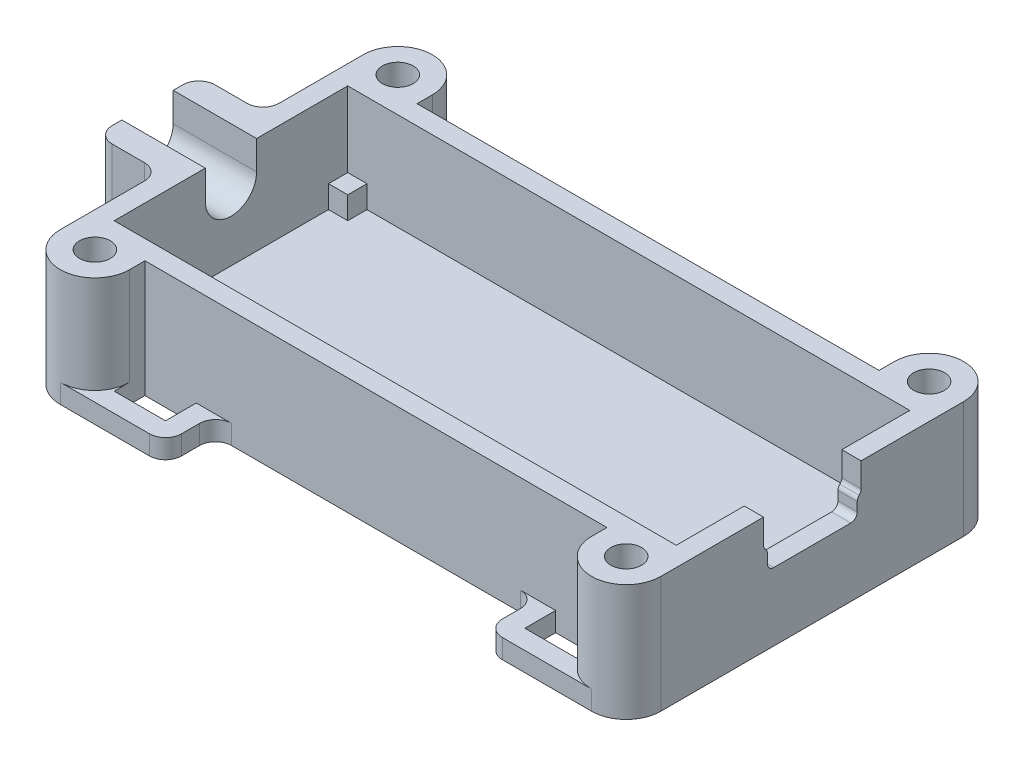
SolidWorks part; units mm, degrees
ref_plane "Front Plane" through (0, 0, 0) normal (0, 0, 1) x (1, 0, 0)
ref_plane "Top Plane" through (0, 0, 0) normal (0, 1, 0) x (1, 0, 0)
ref_plane "Right Plane" through (0, 0, 0) normal (1, 0, 0) x (0, 0, -1)
sketch "Sketch1" plane through (0, 0, 0) normal (0, 1, 0) x (1, 0, 0)
  line L0 (-21.9, 9.1) -> (-23.4, 9.1) construction
  line L1 (-21.9, 9.1) -> (21.9, 9.1)
  line L2 (-21.9, 9.1) -> (-21.9, -9.1)
  line L3 (-21.9, -9.1) -> (21.9, -9.1)
  line L4 (21.9, 9.1) -> (21.9, -9.1)
  line L5 (-21.9, 9.1) -> (21.9, -9.1) construction
  line L6 (-21.9, -9.1) -> (21.9, 9.1) construction
  line L7 (23.4, -10.6) -> (-23.4, -10.6)
  line L8 (23.4, -10.6) -> (23.4, 10.6)
  line L9 (23.4, 10.6) -> (-23.4, 10.6)
  line L10 (-23.4, -10.6) -> (-23.4, 10.6)
  line L11 (23.4, -10.6) -> (-23.4, 10.6) construction
  line L12 (23.4, 10.6) -> (-23.4, -10.6) construction
  line L13 (-21.9, 9.1) -> (-21.9, 10.6) construction
  line L14 (-19.5, 11.8) -> (-18, 11.8) construction
  line L15 (-23.4, 11.8) -> (-23.4, 10.6)
  line L16 (0, 30.5142) -> (0, -27.0472) construction
  line L17 (-40.1948, 0) -> (31.8876, 0) construction
  line L18 (-18, 11.8) -> (-18, 10.6)
  line L19 (18, 11.8) -> (18, 10.6)
  line L20 (23.4, 11.8) -> (23.4, 10.6)
  line L21 (23.4, -11.8) -> (23.4, -10.6)
  line L22 (18, -11.8) -> (18, -10.6)
  line L23 (-18, -11.8) -> (-18, -10.6)
  line L24 (-23.4, -11.8) -> (-23.4, -10.6)
  line L26 (-28.4, 4) -> (-23.4, 4)
  line L27 (-28.4, 4) -> (-28.4, -4)
  line L28 (-28.4, -4) -> (-23.4, -4)
  line L29 (-23.4, 4) -> (-23.4, -4)
  line L30 (-28.4, 4) -> (-23.4, -4) construction
  line L31 (-28.4, -4) -> (-23.4, 4) construction
  circle A0 centre (-20.7, 11.8) radius 1.2
  circle A1 centre (-20.7, 11.8) radius 2.7
  circle A2 centre (20.7, 11.8) radius 1.2
  circle A3 centre (20.7, 11.8) radius 2.7
  circle A4 centre (20.7, -11.8) radius 1.2
  circle A5 centre (20.7, -11.8) radius 2.7
  circle A6 centre (-20.7, -11.8) radius 1.2
  circle A7 centre (-20.7, -11.8) radius 2.7
  point P0 (0, 0)
  point P6 (0, 0)
  point P42 (-25.9, 0)
  dimension "D4" = 2.4
  dimension "D5" = 5
  dimension "D1" = 18.2
  dimension "D2" = 43.8
  dimension "D3" = 1.5
  dimension "D6" = 8
extrude "Boss-Extrude1" add sketch "Sketch1" along normal blind 7.6 contours A1 L9 L18 | L9 A1 A0 | A1 L15 L9 | L9 A3 L19 | A3 L9 A2 | L20 A3 L9 | A5 L7 L22 | A5 L7 A4 | A5 L21 L7 | L24 A7 L7 | A7 L7 A6 | L7 A7 L23 | L7 A7 L3 L2 L1 A1 L9 L10 | A7 L7 | L3 A7 L7 A5 | L7 A5 | A5 L7 L8 L9 A3 L1 L4 L3 | A3 L9 | L1 A3 L9 A1 | A1 L9 | L27 L28 L10 L26 region at (-22.6604, 0, 0) region at (0, 0, -9.8379) region at (-20.7, 0, -9.9829) region at (22.6604, 0, 0) region at (20.7, 0, -9.9829) region at (-23.2639, 0, -11.1989) region at (-23.3164, 0, -10.8968) region at (-18.0836, 0, -10.8968) region at (0, 0, 9.8379) region at (-20.7, 0, 9.9829) region at (18.1361, 0, -11.1989) region at (18.0836, 0, -10.8968) region at (23.3164, 0, -10.8968) region at (20.7, 0, 9.9829) region at (-18.1361, 0, 11.1989) region at (-18.0836, 0, 10.8968) region at (-23.3164, 0, 10.8968) region at (-25.9, 0, 0) region at (23.2639, 0, 11.1989) region at (23.3164, 0, 10.8968) region at (18.0836, 0, 10.8968)
sketch "Sketch3" plane through (0, 0, 0) normal (0, -1, 0) x (1, 0, 0)
  line L8 (-23.4, -4) -> (-23.4, -11.8)
  line L9 (-18, -11.8) -> (-18, -10.6)
  line L10 (-18, -10.6) -> (18, -10.6)
  line L11 (18, -10.6) -> (18, -11.8)
  line L12 (23.4, -11.8) -> (23.4, 11.8)
  line L13 (18, 11.8) -> (18, 10.6)
  line L14 (18, 10.6) -> (-18, 10.6)
  line L15 (-18, 10.6) -> (-18, 11.8)
  line L16 (-23.4, -4) -> (-23.4, -11.8)
  line L17 (-18, -11.8) -> (-18, -10.6)
  line L18 (-18, -10.6) -> (18, -10.6)
  line L19 (18, -10.6) -> (18, -11.8)
  line L20 (23.4, -11.8) -> (23.4, 11.8)
  line L21 (18, 11.8) -> (18, 10.6)
  line L22 (18, 10.6) -> (-18, 10.6)
  line L23 (-18, 10.6) -> (-18, 11.8)
  line L28 (-23.4, 11.8) -> (-23.4, 4)
  line L29 (-23.4, 11.8) -> (-23.4, 4)
  line L30 (-23.4, 4) -> (-28.4, 4)
  line L31 (-23.4, 4) -> (-28.4, 4)
  line L32 (-28.4, 4) -> (-28.4, -4)
  line L33 (-28.4, 4) -> (-28.4, -4)
  line L34 (-28.4, -4) -> (-23.4, -4)
  line L35 (-28.4, -4) -> (-23.4, -4)
  circle A0 centre (-20.7, -11.8) radius 1.2 construction
  circle A1 centre (20.7, -11.8) radius 1.2 construction
  circle A2 centre (20.7, 11.8) radius 1.2 construction
  circle A3 centre (-20.7, 11.8) radius 1.2 construction
  arc A4 (-18, 11.8) -> (-23.4, 11.8) centre (-20.7, 11.8) ccw
  arc A5 (-23.4, -11.8) -> (-18, -11.8) centre (-20.7, -11.8) ccw
  arc A6 (18, -11.8) -> (23.4, -11.8) centre (20.7, -11.8) ccw
  arc A7 (23.4, 11.8) -> (18, 11.8) centre (20.7, 11.8) ccw
  arc A8 (-18, 11.8) -> (-23.4, 11.8) centre (-20.7, 11.8) ccw
  arc A9 (-23.4, -11.8) -> (-18, -11.8) centre (-20.7, -11.8) ccw
  arc A10 (18, -11.8) -> (23.4, -11.8) centre (20.7, -11.8) ccw
  arc A11 (23.4, 11.8) -> (18, 11.8) centre (20.7, 11.8) ccw
  circle A12 centre (-20.7, -11.8) radius 1.2
  circle A13 centre (20.7, -11.8) radius 1.2
  circle A14 centre (20.7, 11.8) radius 1.2
  circle A15 centre (-20.7, 11.8) radius 1.2
  dimension "D1" = 0
extrude "Boss-Extrude2" add sketch "Sketch3" along normal blind 1.5
sketch "Sketch4" plane through (-28.4, 0, 0) normal (-1, 0, 0) x (0, 0, 1)
  line L0 (-9.1, 0) -> (9.1, 0) construction
  line L1 (-9.1, 0) -> (9.1, 0)
  line L2 (0, 7.6) -> (0, -1.5) construction
  line L3 (-4, 7.6) -> (-11.8, 7.6) construction
  line L5 (0, 3.35) -> (11.8, 3.35) construction
  line L6 (11.8, 7.6) -> (11.8, -1.5) construction
  line L7 (-2, 5.35) -> (-2, 7.6)
  line L8 (2, 5.35) -> (2, 7.6)
  line L9 (-2, 7.6) -> (2, 7.6)
  line L11 (-4, 7.6) -> (4, 7.6) construction
  line L12 (4, -1.5) -> (-4, -1.5) construction
  circle A0 centre (0, 5.35) radius 2
  dimension "D2" = 4
  dimension "D1" = 3.35
extrude "Cut-Extrude1" cut sketch "Sketch4" against normal up to next contours A0 L8 L7 | A0 region at (-28.4, 6.475, -1.9541) region at (-28.4, 5.35, 0)
sketch "Sketch5" plane through (0, 0, 0) normal (0, 1, 0) x (1, 0, 0)
  line L0 (0, 18.1559) -> (0, -18.574) construction
  line L1 (-21.9, 9.1) -> (-20.4, 9.1)
  line L2 (-21.9, 9.1) -> (-21.9, 7.6)
  line L3 (-21.9, 7.6) -> (-20.4, 7.6)
  line L4 (-20.4, 9.1) -> (-20.4, 7.6)
  line L5 (-28.7323, 0) -> (29.8474, 0) construction
  line L6 (21.9, 9.1) -> (21.9, 7.6)
  line L7 (21.9, 9.1) -> (20.4, 9.1)
  line L8 (20.4, 9.1) -> (20.4, 7.6)
  line L9 (21.9, 7.6) -> (20.4, 7.6)
  line L10 (-21.9, -9.1) -> (-21.9, -7.6)
  line L11 (-21.9, -9.1) -> (-20.4, -9.1)
  line L12 (-20.4, -9.1) -> (-20.4, -7.6)
  line L13 (-21.9, -7.6) -> (-20.4, -7.6)
  line L14 (21.9, -9.1) -> (21.9, -7.6)
  line L15 (21.9, -9.1) -> (20.4, -9.1)
  line L16 (20.4, -9.1) -> (20.4, -7.6)
  line L17 (21.9, -7.6) -> (20.4, -7.6)
  dimension "D1" = 1.5
extrude "Boss-Extrude3" add sketch "Sketch5" along normal blind 1.75
sketch "Sketch6" plane through (23.4, 0, 0) normal (1, 0, 0) x (0, 0, -1)
  line L1 (0, 7.6) -> (0, -1.5) construction
  line L2 (11.8, 7.6) -> (-11.8, 7.6) construction
  line L3 (11.8, -1.5) -> (-11.8, -1.5) construction
  line L4 (7.6, 0) -> (-7.6, 0) construction
  line L5 (7.6, 0) -> (-7.6, 0)
  line L6 (-3.8, 5.2) -> (3.8, 5.2) construction
  line L7 (-3.8, 7.6) -> (3.8, 7.6)
  line L8 (-3.8, 7.6) -> (-3.8, 3.8)
  line L9 (-3.8, 3.8) -> (3.8, 3.8)
  line L10 (3.8, 7.6) -> (3.8, 3.8)
  line L11 (-3.8, 7.6) -> (3.8, 3.8) construction
  line L12 (-3.8, 3.8) -> (3.8, 7.6) construction
  line L13 (-3.5, 5.2) -> (-3.5, 3.8)
  line L14 (-3.5, 5.2) -> (-3.8, 5.5)
  line L15 (3.5, 5.2) -> (3.5, 3.8)
  line L16 (3.5, 5.2) -> (3.8, 5.5)
  point P8 (0, 5.7)
  line M9 (11.8, 7.6) -> (-11.8, 7.6)
  dimension "D1" = 3.8
  dimension "D2" = 7.6
  dimension "D3" = 1.4
  dimension "D4" = 7
  dimension "D5" = 45
extrude "Cut-Extrude2" cut sketch "Sketch6" against normal up to next contours L10 L8 L9 M9 region at (23.4, 5.7374, 0)
sketch "Sketch8" plane through (0, -1.5, 0) normal (0, -1, 0) x (1, 0, 0)
  line L0 (-20.7, 14.5) -> (-12.5, 14.5)
  line L1 (-18, 10.6) -> (-14, 10.6)
  line L2 (-18, 10.6) -> (-18, 13)
  line L3 (-18, 13) -> (-14, 13)
  line L4 (-14, 10.6) -> (-14, 13)
  line L5 (-12.5, 14.5) -> (-12.5, 10.6)
  line L6 (18, 10.6) -> (-18, 10.6) construction
  line L7 (-14, 13) -> (-14, 14.5) construction
  line L8 (-14, 13) -> (-12.5, 13) construction
  line L9 (0, 29.3193) -> (0, -24.0926) construction
  line L10 (-37.5157, 0) -> (37.6606, 0) construction
  line L11 (18, 10.6) -> (14, 10.6)
  line L12 (18, 10.6) -> (18, 13)
  line L13 (18, 13) -> (14, 13)
  line L14 (14, 10.6) -> (14, 13)
  line L15 (12.5, 14.5) -> (12.5, 10.6)
  line L16 (20.7, 14.5) -> (12.5, 14.5)
  line L17 (-12.5, -14.5) -> (-12.5, -10.6)
  line L18 (-20.7, -14.5) -> (-12.5, -14.5)
  line L19 (-18, -10.6) -> (-14, -10.6)
  line L20 (-18, -10.6) -> (-18, -13)
  line L21 (-18, -13) -> (-14, -13)
  line L22 (-14, -10.6) -> (-14, -13)
  line L23 (20.7, -14.5) -> (12.5, -14.5)
  line L24 (12.5, -14.5) -> (12.5, -10.6)
  line L25 (14, -10.6) -> (14, -13)
  line L26 (18, -13) -> (14, -13)
  line L27 (18, -10.6) -> (18, -13)
  line L28 (18, -10.6) -> (14, -10.6)
  arc A0 (-18, 11.8) -> (-23.4, 11.8) centre (-20.7, 11.8) ccw construction
  arc M20 (-23.4, -11.8) -> (-18, -11.8) centre (-20.7, -11.8) ccw
  line M22 (-18, -10.6) -> (18, -10.6)
  arc M24 (18, -11.8) -> (23.4, -11.8) centre (20.7, -11.8) ccw
  arc M26 (23.4, 11.8) -> (18, 11.8) centre (20.7, 11.8) ccw
  line M28 (18, 10.6) -> (-18, 10.6)
  arc M30 (-18, 11.8) -> (-23.4, 11.8) centre (-20.7, 11.8) ccw
  dimension "D1" = 2.4
  dimension "D2" = 4
extrude "Boss-Extrude4" add sketch "Sketch8" against normal blind 1.5 contours L5 L0 L2 L3 L4 M30 M28 | L16 L15 L14 L13 L12 M26 M28 | L27 L26 L25 L24 L23 M24 M22 | L22 L21 L20 L18 L17 M22 M20 region at (15.1043, -1.5, 13.2438) region at (-15.1043, -1.5, 13.2438) region at (-15.1043, -1.5, -13.2438) region at (15.1043, -1.5, -13.2438)
fillet "Fillet1" radius 1.25 12 edges at (-28.4, 3.05, 4) (-28.4, 3.05, -4) (-23.4, 3.05, -4) (-23.4, 3.05, 4) (-12.5, -0.75, -10.6) (-12.5, -0.75, -14.5) (12.5, -0.75, -14.5) (12.5, -0.75, -10.6) (12.5, -0.75, 14.5) (12.5, -0.75, 10.6) (-12.5, -0.75, 10.6) (-12.5, -0.75, 14.5)
fillet "Fillet2" radius 0.5 6 edges at (22.65, 3.8, 3.5) (22.65, 3.8, -3.5) (22.65, 5.2, -3.5) (22.65, 5.5, -3.8) (22.65, 5.2, 3.5) (22.65, 5.5, 3.8)
